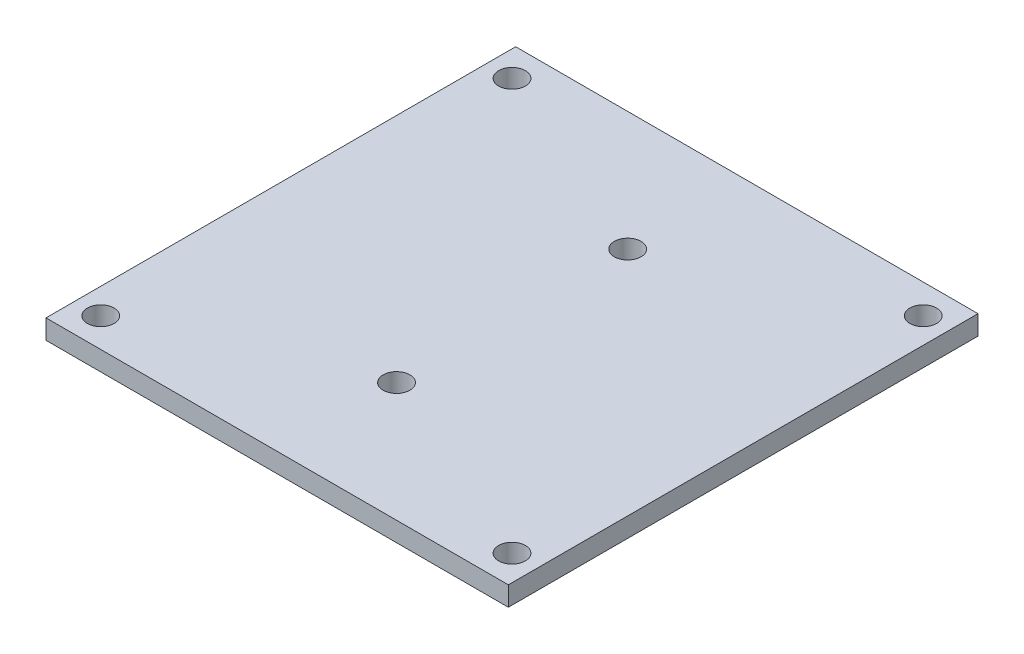
SolidWorks part; units mm, degrees
ref_plane "Front Plane" through (0, 0, 0) normal (0, 0, 1) x (1, 0, 0)
ref_plane "Top Plane" through (0, 0, 0) normal (0, 1, 0) x (1, 0, 0)
ref_plane "Right Plane" through (0, 0, 0) normal (1, 0, 0) x (0, 0, -1)
sketch "Sketch1" plane through (0, 0, 0) normal (0, 1, 0) x (1, 0, 0)
  line L0 (-7.4919, 7.6) -> (-1.9919, 7.6)
  line L1 (-19, -19.3) -> (19, -19.3)
  line L2 (-19, -19.3) -> (-19, 19.3)
  line L3 (-19, 19.3) -> (19, 19.3)
  line L4 (19, -19.3) -> (19, 19.3)
  line L5 (-19, -19.3) -> (19, 19.3) construction
  line L6 (-19, 19.3) -> (19, -19.3) construction
  line L7 (2.0081, 9.5) -> (2.0081, 7.6)
  line L8 (-1.9919, 7.6) -> (-1.9919, 9.5)
  line L9 (-1.9919, -7.6) -> (-7.4919, -7.6)
  line L10 (-1.9919, -9.5) -> (-1.9919, -7.6)
  line L11 (2.0081, -7.6) -> (2.0081, -9.5)
  line L12 (7.5081, -7.6) -> (2.0081, -7.6)
  line L13 (7.5081, 7.6) -> (7.5081, -7.6)
  line L14 (2.0081, 7.6) -> (7.5081, 7.6)
  line L15 (-7.4919, -7.6) -> (-7.4919, 7.6)
  line L16 (-19, 0) -> (19, 0) construction
  line L17 (0, 19.3) -> (0, -19.3) construction
  line L19 (-16, -14.3) -> (16, -14.3)
  line L20 (-16, -14.3) -> (-16, 14.3)
  line L21 (-16, 14.3) -> (16, 14.3)
  line L22 (16, -14.3) -> (16, 14.3)
  line L23 (-16, -14.3) -> (16, 14.3) construction
  line L24 (-16, 14.3) -> (16, -14.3) construction
  arc A0 (2.0081, 9.5) -> (-1.9919, 9.5) centre (0.0081, 9.5) ccw
  arc A3 (-1.9919, -9.5) -> (2.0081, -9.5) centre (0.0081, -9.5) ccw
  circle A6 centre (0.0081, 9.5) radius 1.1
  circle A7 centre (0.0081, -9.5) radius 1.1
  circle A8 centre (-16.9, 16.9) radius 1.1
  circle A9 centre (16.9, 16.9) radius 1.1
  circle A10 centre (16.9, -16.9) radius 1.1
  circle A11 centre (-16.9, -16.9) radius 1.1
  point P0 (0, 0)
  point P34 (7.5081, 0)
  point P35 (-7.4919, 0)
  point P36 (0, 0)
  dimension "D3" = 2.2
  dimension "D6" = 2
  dimension "D7" = 2.2
  dimension "D8" = 2.4
  dimension "D9" = 2.1
  dimension "D1" = 38.6
  dimension "D2" = 38
  dimension "D4" = 15.2
  dimension "D5" = 15
  dimension "D10" = 11.5081
  dimension "D11" = 5.5
  dimension "D12" = 4
  dimension "D13" = 19
  dimension "D14" = 3
  dimension "D15" = 5
extrude "Boss-Extrude1" add sketch "Sketch1" along normal blind 1.6 contours L1 L4 L3 L2 A9 A8 L22 L19 L20 L21 A10 A11 | L19 L22 L21 L20 A3 L10 L9 L15 L0 L8 A0 L7 L14 L13 L12 L11 | L10 A3 L11 L12 L13 L14 L7 A0 L8 L0 L15 L9 A6 A7 region at (0.0081, 0, 0) region at (-18.4583, 0, 0) region at (-15.5708, 0, 0)
extrude "Boss-Extrude2" add sketch "Sketch1<3>" against normal blind 2.3 contours L19 L22 L21 L20 A3 L10 L9 L15 L0 L8 A0 L7 L14 L13 L12 L11 | L10 A3 L11 L12 L13 L14 L7 A0 L8 L0 L15 L9 A6 A7 region at (0.0081, 0, 0) region at (-15.5708, 0, 0)
sketch "Sketch1<3>" plane through (0, 0, 0) normal (0, 1, 0) x (1, 0, 0) same geometry as "Sketch1"
